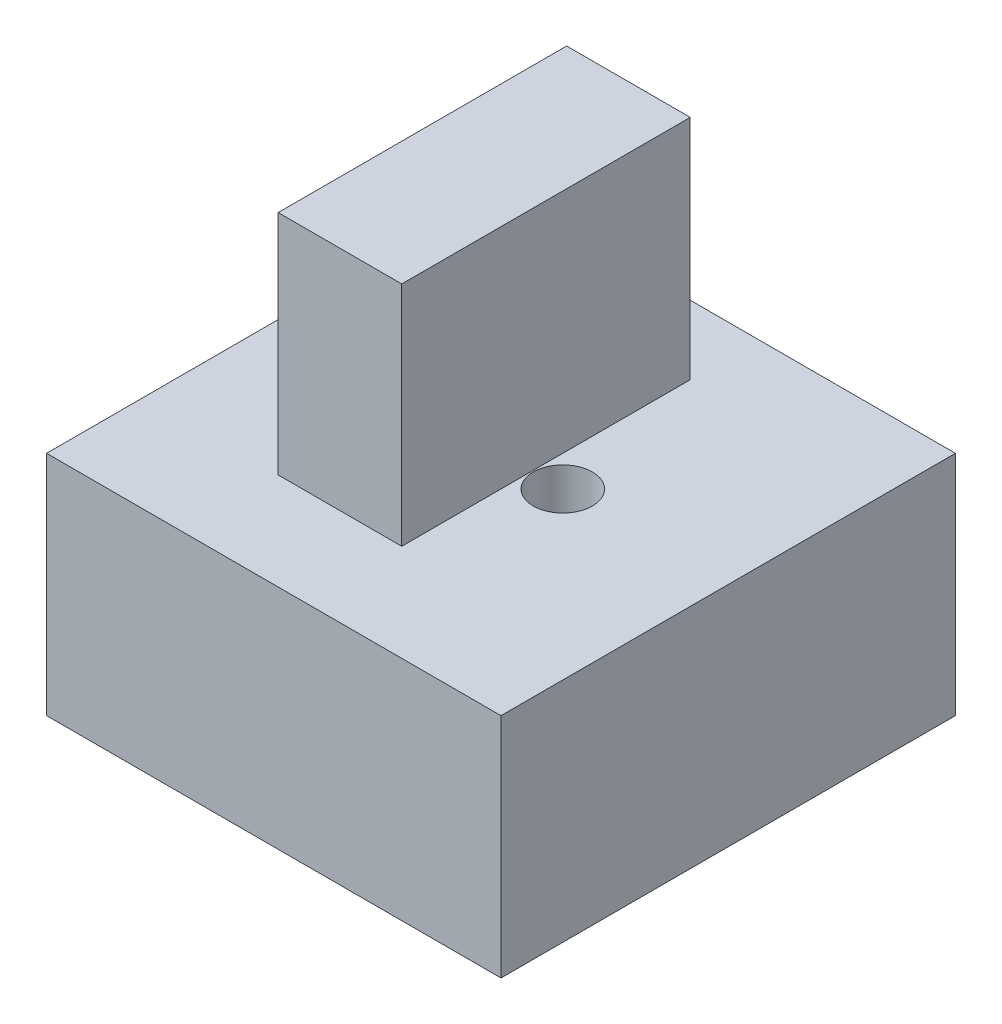
SolidWorks part; units mm, degrees
ref_plane "Front Plane" through (0, 0, 0) normal (0, 0, 1) x (1, 0, 0)
ref_plane "Top Plane" through (0, 0, 0) normal (0, 1, 0) x (1, 0, 0)
ref_plane "Right Plane" through (0, 0, 0) normal (1, 0, 0) x (0, 0, -1)
sketch "Sketch1" plane through (0, 0, 0) normal (0, 1, 0) x (1, 0, 0)
  line L1 (-5, -5) -> (5, -5)
  line L2 (-5, -5) -> (-5, 5)
  line L3 (-5, 5) -> (5, 5)
  line L4 (5, -5) -> (5, 5)
  line L5 (-5, -5) -> (5, 5) construction
  line L6 (-5, 5) -> (5, -5) construction
  circle A0 centre (0, 0) radius 0.65
  circle A1 centre (1.36, 0) radius 0.65
  circle A2 centre (-1.36, 0) radius 0.65
  circle A3 centre (-2.72, 0) radius 0.65
  point P0 (0, 0)
  dimension "D3" = 1.3
  dimension "D1" = 10
  dimension "D2" = 10
  dimension "D4" = 1.36
  dimension "D5" = 1.36
  dimension "D6" = 1.36
extrude "Boss-Extrude1" add sketch "Sketch1" along normal blind 5
sketch "Sketch2" plane through (0, 5, 0) normal (0, 1, 0) x (1, 0, 0)
  line L0 (-2.72, 0.65) -> (-1.36, 0.65) construction
  line L1 (0, 0.65) -> (1.36, 0.65) construction
  line L2 (-2.04, 3.4847) -> (-2.04, -2.8643)
  line L3 (0.68, 3.4847) -> (0.68, -2.8643)
  line L4 (-2.04, 3.4847) -> (0.68, 3.4847)
  line L5 (0.68, -2.8643) -> (-2.04, -2.8643)
  circle A0 centre (-2.72, 0) radius 0.65 construction
  circle A1 centre (-1.36, 0) radius 0.65 construction
  circle A2 centre (0, 0) radius 0.65 construction
  circle A3 centre (1.36, 0) radius 0.65 construction
  point P14 (-2.04, 0.65)
  point P17 (0.68, 0.65)
extrude "Boss-Extrude2" add sketch "Sketch2" along normal blind 5
